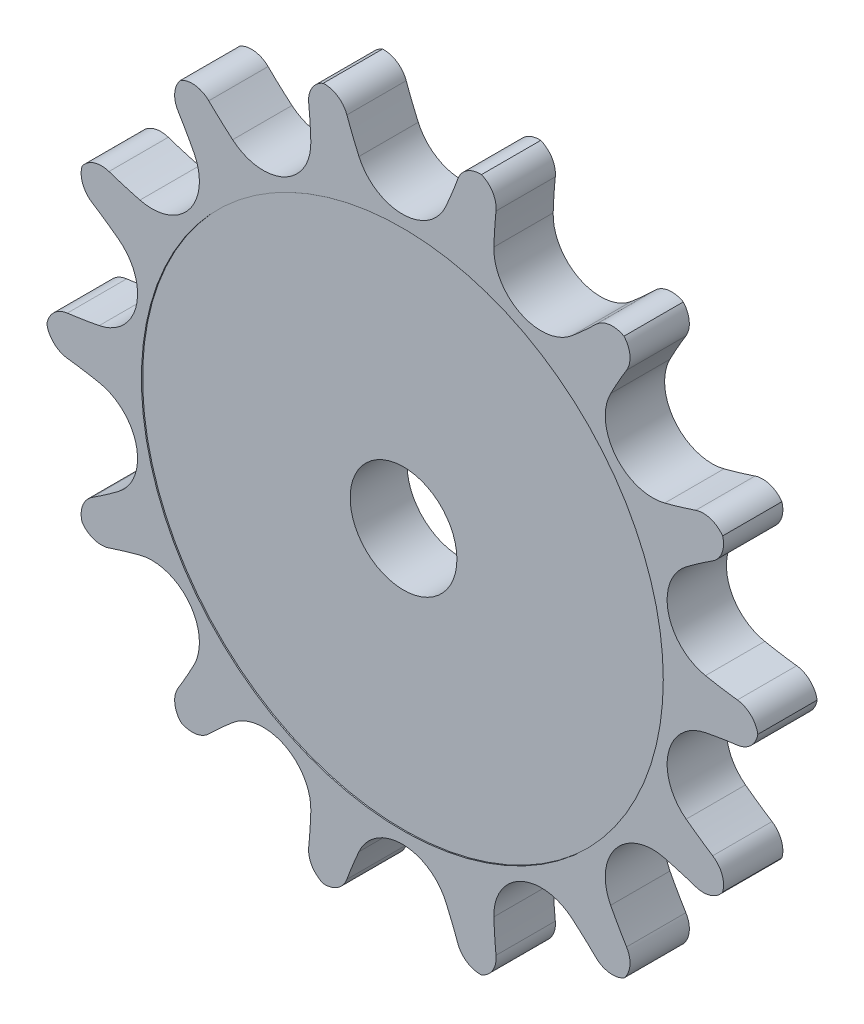
SolidWorks part; units mm, degrees
ref_plane "前视基准面" through (0, 0, 0) normal (0, 0, 1) x (1, 0, 0)
ref_plane "上视基准面" through (0, 0, 0) normal (0, 1, 0) x (1, 0, 0)
ref_plane "右视基准面" through (0, 0, 0) normal (1, 0, 0) x (0, 0, -1)
sketch "草图1" plane through (0, 0, 0) normal (0, 0, 1) x (1, 0, 0)
  circle A0 centre (0, 0) radius 30
  dimension "D1" = 60
extrude "凸台-拉伸1" add sketch "草图1" along normal blind 5
sketch "草图2" plane through (0, 0, 5) normal (0, 0, 1) x (1, 0, 0)
  circle A0 centre (0, 0) radius 4.5
  dimension "D1" = 9
extrude "切除-拉伸1" cut sketch "草图2" against normal through all
sketch "草图3" plane through (0, 0, 0) normal (0, 0, 1) x (1, 0, 0)
  line L0 (0, 62.5305) -> (0, -57.8512) construction
  arc A0 (-3.6568, 25.379) -> (3.6568, 25.379) centre (0, 27) ccw
  arc A1 (3.6568, 25.379) -> (5.2308, 29.5405) centre (-32.9115, 41.5887) ccw
  arc A2 (-3.6568, 25.379) -> (-5.2308, 29.5405) centre (32.9115, 41.5887) cw
  circle A3 centre (0, 0) radius 30 construction
  arc A4 (5.2308, 29.5405) -> (-5.2308, 29.5405) centre (0, 0) ccw
  dimension "D1" = 4
  dimension "D2" = 40
  dimension "D3" = 27
extrude "切除-拉伸7" cut sketch "草图3" along normal through all contours L0 A4 A2 A0 | A4 L0 A0 A1 region at (2.0555, 26.9596, 0) region at (-2.0555, 26.9596, 0)
pattern_circular "阵列(圆周)1" count 14 over 360 about axis through (0, 0, 0) along (0, 0, 1) of "切除-拉伸7"
fillet "圆角3" radius 2 28 edges at (5.2308, 29.5405, 2.5) (-5.2308, 29.5405, 2.5) (-8.1043, 28.8846, 2.5) (-17.5299, 24.3455, 2.5) (-19.8343, 22.5078, 2.5) (-26.357, 14.3286, 2.5) (-27.6358, 11.673, 2.5) (-29.9638, -1.4737, 2.5) (-29.9638, 1.4737, 2.5) (-27.6358, -11.673, 2.5) (-26.357, -14.3286, 2.5) (-19.8343, -22.5078, 2.5) (-17.5299, -24.3455, 2.5) (-8.1043, -28.8846, 2.5) (-5.2308, -29.5405, 2.5) (5.2308, -29.5405, 2.5) (8.1043, -28.8846, 2.5) (17.5299, -24.3455, 2.5) (19.8343, -22.5078, 2.5) (26.357, -14.3286, 2.5) (27.6358, -11.673, 2.5) (29.9638, -1.4737, 2.5) (29.9638, 1.4737, 2.5) (27.6358, 11.673, 2.5) (26.357, 14.3286, 2.5) (19.8343, 22.5078, 2.5) (17.5299, 24.3455, 2.5) (8.1043, 28.8846, 2.5)
sketch "草图4" plane through (0, 0, 5) normal (0, 0, 1) x (1, 0, 0)
  circle A0 centre (0, 0) radius 22
extrude "切除-拉伸9" cut sketch "草图4" against normal blind 0.1
sketch "草图5" plane through (0, 0, 0) normal (0, 0, -1) x (-1, 0, 0)
  circle A0 centre (0, 0) radius 22
extrude "切除-拉伸10" cut sketch "草图5" against normal blind 0.1
